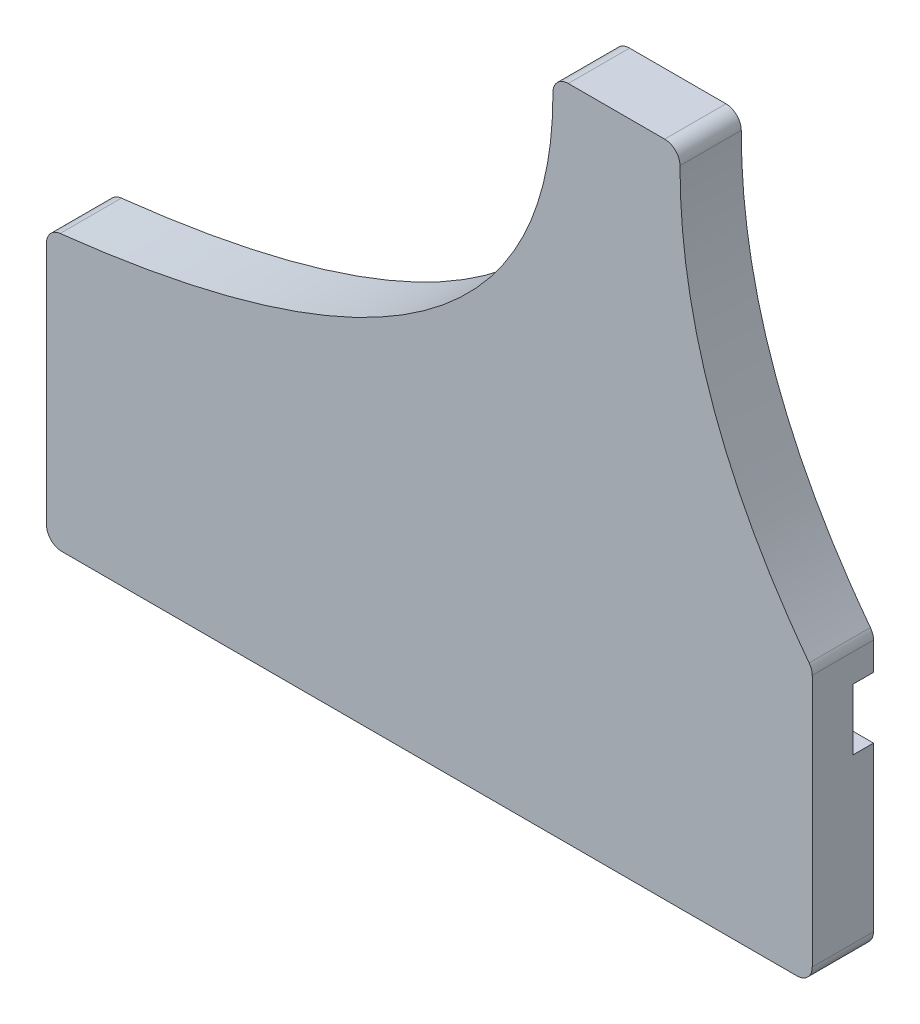
SolidWorks part; units mm, degrees
ref_plane "Ebene vorne" through (0, 0, 0) normal (0, 0, 1) x (1, 0, 0)
ref_plane "Ebene oben" through (0, 0, 0) normal (0, 1, 0) x (1, 0, 0)
ref_plane "Ebene rechts" through (0, 0, 0) normal (1, 0, 0) x (0, 0, -1)
sketch "Skizze1" plane through (0, 0, 0) normal (0, 0, 1) x (1, 0, 0)
  line L0 (24.14, 88) -> (49.14, 88)
  line L3 (75, 12.5) -> (75, -41)
  line L4 (75, -41) -> (-75, -41)
  line L9 (-75, -41) -> (-75, 12.5)
  line L13 (30.64, 81.5) -> (42.64, 81.5)
  line L14 (30.64, 81.5) -> (30.64, 26.5)
  line L15 (30.64, 26.5) -> (42.64, 26.5)
  line L16 (42.64, 81.5) -> (42.64, 26.5)
  line L17 (30.64, 81.5) -> (42.64, 26.5) construction
  line L18 (30.64, 26.5) -> (42.64, 81.5) construction
  line L19 (-75, 6) -> (75, 6)
  line L20 (-75, 6) -> (-75, -6)
  line L21 (-75, -6) -> (75, -6)
  line L22 (75, 6) -> (75, -6)
  line L23 (-75, 6) -> (75, -6) construction
  line L24 (-75, -6) -> (75, 6) construction
  line L26 (-75, 12.5) -> (75, 12.5) construction
  line L27 (24.14, 81.5) -> (49.14, 81.5) construction
  spline S0 degree 2 poles (24.14, 88) (26.8075, 22.9626) (-75, 12.5) knots 0 0 0 1 1 1
  spline S1 degree 2 poles (49.14, 88) (47.9994, 47.6999) (75, 12.5) knots 0 0 0 1 1 1
  point P2 (0, -41)
  point P13 (36.64, 88)
  point P16 (36.64, 54)
  point P23 (0, 0)
  dimension "D2" = 25
  dimension "D3" = 150
  dimension "D4" = 35
  dimension "D5" = 36.64
  dimension "D6" = 6.5
  dimension "D7" = 69
  dimension "D8" = 6.5
  dimension "D9" = 12
  dimension "D10" = 55
  dimension "D11" = 12
extrude "Aufsatz-Linear austragen1" add sketch "Skizze1" along normal blind 12 contours S1 L0 S0 L9 L19 L3 L13 L16 L15 L14 | L16 L13 L14 L15 | L9 L21 L3 L19 | L21 L9 L4 L3 region at (18.2385, 29.5651, 0) region at (0, 0, 0) region at (0, -23.5, 0) region at (36.64, 54, 0)
extrude "Schnitt-Linear austragen2" cut sketch "Skizze1<4>" along normal blind 4 contours L16 L13 L14 L15 | L20 L19 L22 L21 region at (36.64, 54, 0)
sketch "Skizze1<4>" plane through (0, 0, 0) normal (0, 0, 1) x (1, 0, 0) same geometry as "Skizze1"
fillet "Verrundung1" radius 3 6 edges at (75, -41, 6) (75, 12.5, 6) (49.14, 88, 6) (-75, -41, 6) (-75, 12.5, 6) (24.14, 88, 6)
